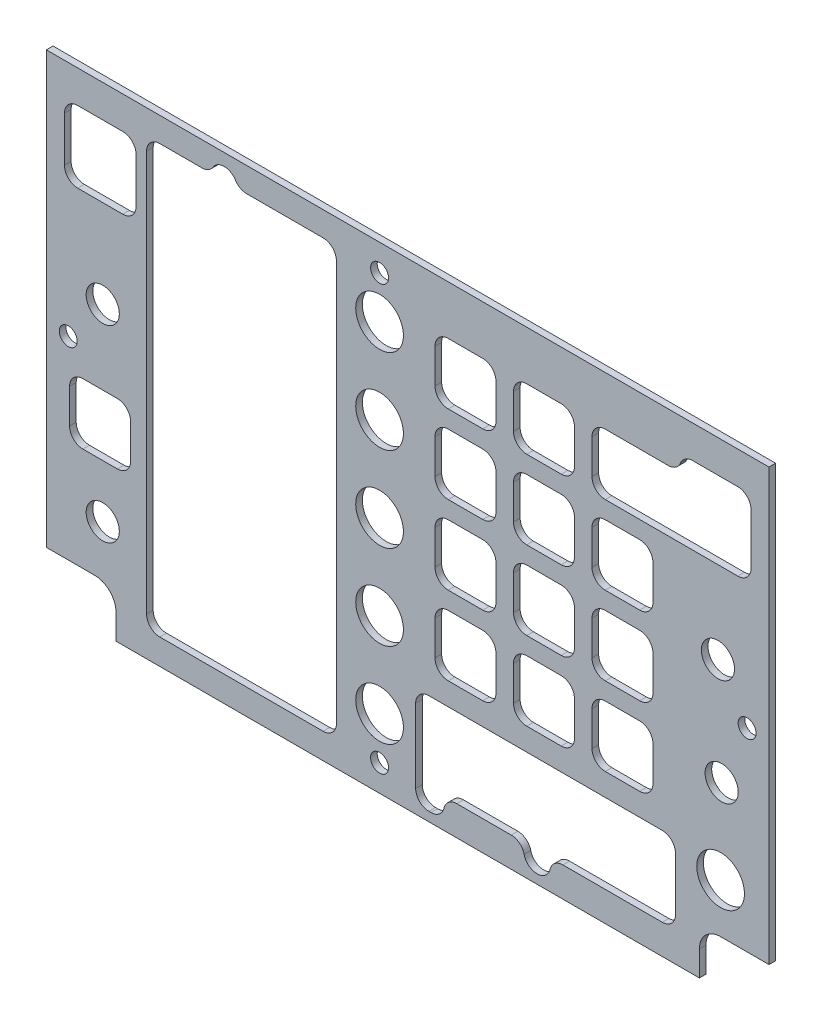
SolidWorks part; units mm, degrees
material "ABS PC"
ref_plane "Front Plane" through (0, 0, 0) normal (0, 0, 1) x (1, 0, 0)
ref_plane "Top Plane" through (0, 0, 0) normal (0, 1, 0) x (1, 0, 0)
ref_plane "Right Plane" through (0, 0, 0) normal (1, 0, 0) x (0, 0, -1)
sketch "Sketch1" plane through (0, 0, 0) normal (0, 0, 1) x (1, 0, 0)
  line L8 (74.93, -171.1167) -> (86.5187, -171.1167)
  line L9 (86.5187, -171.1167) -> (86.5187, -67.9292)
  line L10 (86.5187, -67.9292) -> (-86.5187, -67.9292)
  line L11 (-86.5187, -67.9292) -> (-86.5187, -171.1167)
  line L12 (-86.5187, -171.1167) -> (-74.93, -171.1167)
  line L13 (-69.85, -176.1967) -> (-69.85, -182.2292)
  line L14 (-69.85, -182.2292) -> (69.85, -182.2292)
  line L15 (69.85, -182.2292) -> (69.85, -176.1967)
  line L16 (74.93, -171.1167) -> (86.5187, -171.1167)
  line L17 (86.5187, -171.1167) -> (86.5187, -67.9292)
  line L18 (86.5187, -67.9292) -> (-86.5187, -67.9292)
  line L19 (-86.5187, -67.9292) -> (-86.5187, -171.1167)
  line L20 (-86.5187, -171.1167) -> (-74.93, -171.1167)
  line L21 (-69.85, -176.1967) -> (-69.85, -182.2292)
  line L22 (-69.85, -182.2292) -> (69.85, -182.2292)
  line L23 (69.85, -182.2292) -> (69.85, -176.1967)
  arc A2 (-69.85, -176.1967) -> (-74.93, -171.1167) centre (-74.93, -176.1967) ccw
  arc A3 (74.93, -171.1167) -> (69.85, -176.1967) centre (74.93, -176.1967) ccw
  arc A4 (-69.85, -176.1967) -> (-74.93, -171.1167) centre (-74.93, -176.1967) ccw
  arc A5 (74.93, -171.1167) -> (69.85, -176.1967) centre (74.93, -176.1967) ccw
  dimension "D1" = 0
extrude "Boss-Extrude1" add sketch "Sketch1" against normal blind 1.5875
sketch "Sketch3" plane through (0, 0, 0) normal (0, 0, 1) x (1, 0, 0)
  line L0 (-67.6275, -133.0167) -> (-79.6925, -133.0167) construction
  line L1 (-79.6925, -133.0167) -> (-79.6925, -145.0817) construction
  line L2 (-79.6925, -145.0817) -> (-67.6275, -145.0817) construction
  line L3 (-67.6275, -145.0817) -> (-67.6275, -133.0167) construction
  line L4 (19.8755, -149.3997) -> (19.8755, -137.3347) construction
  line L5 (19.8755, -137.3347) -> (7.8105, -137.3347) construction
  line L6 (7.8105, -137.3347) -> (7.8105, -149.3997) construction
  line L7 (7.8105, -149.3997) -> (19.8755, -149.3997) construction
  line L8 (38.6715, -149.3997) -> (38.6715, -137.3347) construction
  line L9 (38.6715, -137.3347) -> (26.6065, -137.3347) construction
  line L10 (26.6065, -137.3347) -> (26.6065, -149.3997) construction
  line L11 (26.6065, -149.3997) -> (38.6715, -149.3997) construction
  line L12 (45.4025, -149.3997) -> (57.4675, -149.3997) construction
  line L13 (57.4675, -149.3997) -> (57.4675, -137.3347) construction
  line L14 (57.4675, -137.3347) -> (45.4025, -137.3347) construction
  line L15 (45.4025, -137.3347) -> (45.4025, -149.3997) construction
  line L16 (57.4675, -130.6037) -> (57.4675, -118.5387) construction
  line L17 (57.4675, -118.5387) -> (45.4025, -118.5387) construction
  line L18 (45.4025, -118.5387) -> (45.4025, -130.6037) construction
  line L19 (45.4025, -130.6037) -> (57.4675, -130.6037) construction
  line L20 (38.6715, -130.6037) -> (38.6715, -118.5387) construction
  line L21 (38.6715, -118.5387) -> (26.6065, -118.5387) construction
  line L22 (26.6065, -118.5387) -> (26.6065, -130.6037) construction
  line L23 (26.6065, -130.6037) -> (38.6715, -130.6037) construction
  line L24 (19.8755, -130.6037) -> (19.8755, -118.5387) construction
  line L25 (19.8755, -118.5387) -> (7.8105, -118.5387) construction
  line L26 (7.8105, -118.5387) -> (7.8105, -130.6037) construction
  line L27 (7.8105, -130.6037) -> (19.8755, -130.6037) construction
  line L28 (19.8755, -111.8077) -> (19.8755, -99.7427) construction
  line L29 (19.8755, -99.7427) -> (7.8105, -99.7427) construction
  line L30 (7.8105, -99.7427) -> (7.8105, -111.8077) construction
  line L31 (7.8105, -111.8077) -> (19.8755, -111.8077) construction
  line L32 (19.8755, -93.0117) -> (19.8755, -80.9467) construction
  line L33 (19.8755, -80.9467) -> (7.8105, -80.9467) construction
  line L34 (7.8105, -80.9467) -> (7.8105, -93.0117) construction
  line L35 (7.8105, -93.0117) -> (19.8755, -93.0117) construction
  line L36 (38.6715, -93.0117) -> (38.6715, -80.9467) construction
  line L37 (38.6715, -80.9467) -> (26.6065, -80.9467) construction
  line L38 (26.6065, -80.9467) -> (26.6065, -93.0117) construction
  line L39 (26.6065, -93.0117) -> (38.6715, -93.0117) construction
  line L40 (38.6715, -111.8077) -> (38.6715, -99.7427) construction
  line L41 (38.6715, -99.7427) -> (26.6065, -99.7427) construction
  line L42 (26.6065, -99.7427) -> (26.6065, -111.8077) construction
  line L43 (26.6065, -111.8077) -> (38.6715, -111.8077) construction
  line L44 (57.4675, -111.8077) -> (57.4675, -99.7427) construction
  line L45 (57.4675, -99.7427) -> (45.4025, -99.7427) construction
  line L46 (45.4025, -99.7427) -> (45.4025, -111.8077) construction
  line L47 (45.4025, -111.8077) -> (57.4675, -111.8077) construction
  line L48 (57.4675, -93.0117) -> (57.4675, -80.9467) construction
  line L49 (57.4675, -80.9467) -> (45.4025, -80.9467) construction
  line L50 (45.4025, -80.9467) -> (45.4025, -93.0117) construction
  line L51 (45.4025, -93.0117) -> (57.4675, -93.0117) construction
  line L52 (-67.6275, -133.0167) -> (-79.6925, -133.0167)
  line L53 (-79.6925, -133.0167) -> (-79.6925, -145.0817)
  line L54 (-79.6925, -145.0817) -> (-67.6275, -145.0817)
  line L55 (-67.6275, -145.0817) -> (-67.6275, -133.0167)
  line L56 (19.8755, -149.3997) -> (19.8755, -137.3347)
  line L57 (19.8755, -137.3347) -> (7.8105, -137.3347)
  line L58 (7.8105, -137.3347) -> (7.8105, -149.3997)
  line L59 (7.8105, -149.3997) -> (19.8755, -149.3997)
  line L60 (38.6715, -149.3997) -> (38.6715, -137.3347)
  line L61 (38.6715, -137.3347) -> (26.6065, -137.3347)
  line L62 (26.6065, -137.3347) -> (26.6065, -149.3997)
  line L63 (26.6065, -149.3997) -> (38.6715, -149.3997)
  line L64 (45.4025, -149.3997) -> (57.4675, -149.3997)
  line L65 (57.4675, -149.3997) -> (57.4675, -137.3347)
  line L66 (57.4675, -137.3347) -> (45.4025, -137.3347)
  line L67 (45.4025, -137.3347) -> (45.4025, -149.3997)
  line L68 (57.4675, -130.6037) -> (57.4675, -118.5387)
  line L69 (57.4675, -118.5387) -> (45.4025, -118.5387)
  line L70 (45.4025, -118.5387) -> (45.4025, -130.6037)
  line L71 (45.4025, -130.6037) -> (57.4675, -130.6037)
  line L72 (38.6715, -130.6037) -> (38.6715, -118.5387)
  line L73 (38.6715, -118.5387) -> (26.6065, -118.5387)
  line L74 (26.6065, -118.5387) -> (26.6065, -130.6037)
  line L75 (26.6065, -130.6037) -> (38.6715, -130.6037)
  line L76 (19.8755, -130.6037) -> (19.8755, -118.5387)
  line L77 (19.8755, -118.5387) -> (7.8105, -118.5387)
  line L78 (7.8105, -118.5387) -> (7.8105, -130.6037)
  line L79 (7.8105, -130.6037) -> (19.8755, -130.6037)
  line L80 (19.8755, -111.8077) -> (19.8755, -99.7427)
  line L81 (19.8755, -99.7427) -> (7.8105, -99.7427)
  line L82 (7.8105, -99.7427) -> (7.8105, -111.8077)
  line L83 (7.8105, -111.8077) -> (19.8755, -111.8077)
  line L84 (19.8755, -93.0117) -> (19.8755, -80.9467)
  line L85 (19.8755, -80.9467) -> (7.8105, -80.9467)
  line L86 (7.8105, -80.9467) -> (7.8105, -93.0117)
  line L87 (7.8105, -93.0117) -> (19.8755, -93.0117)
  line L88 (38.6715, -93.0117) -> (38.6715, -80.9467)
  line L89 (38.6715, -80.9467) -> (26.6065, -80.9467)
  line L90 (26.6065, -80.9467) -> (26.6065, -93.0117)
  line L91 (26.6065, -93.0117) -> (38.6715, -93.0117)
  line L92 (38.6715, -111.8077) -> (38.6715, -99.7427)
  line L93 (38.6715, -99.7427) -> (26.6065, -99.7427)
  line L94 (26.6065, -99.7427) -> (26.6065, -111.8077)
  line L95 (26.6065, -111.8077) -> (38.6715, -111.8077)
  line L96 (57.4675, -111.8077) -> (57.4675, -99.7427)
  line L97 (57.4675, -99.7427) -> (45.4025, -99.7427)
  line L98 (45.4025, -99.7427) -> (45.4025, -111.8077)
  line L99 (45.4025, -111.8077) -> (57.4675, -111.8077)
  line L100 (57.4675, -93.0117) -> (57.4675, -80.9467)
  line L101 (57.4675, -80.9467) -> (45.4025, -80.9467)
  line L102 (45.4025, -80.9467) -> (45.4025, -93.0117)
  line L103 (45.4025, -93.0117) -> (57.4675, -93.0117)
  circle A0 centre (74.93, -159.3692) radius 4.445 construction
  circle A1 centre (-6.731, -165.7192) radius 4.445 construction
  circle A2 centre (-6.731, -145.3992) radius 4.445 construction
  circle A3 centre (-6.731, -125.0792) radius 4.445 construction
  circle A4 centre (-6.731, -104.7592) radius 4.445 construction
  circle A5 centre (-6.731, -84.4392) radius 4.445 construction
  circle A6 centre (74.93, -159.3692) radius 4.445
  circle A7 centre (-6.731, -165.7192) radius 4.445
  circle A8 centre (-6.731, -145.3992) radius 4.445
  circle A9 centre (-6.731, -125.0792) radius 4.445
  circle A10 centre (-6.731, -104.7592) radius 4.445
  circle A11 centre (-6.731, -84.4392) radius 4.445
extrude "Cut-Extrude1" [suppressed] cut sketch "Sketch3" against normal through all
sketch "Sketch4" plane through (0, 0, 0) normal (0, 0, 1) x (1, 0, 0)
  circle A0 centre (-73.025, -113.9667) radius 3.9688
  circle A1 centre (-73.025, -159.0517) radius 3.9688
  circle A2 centre (74.295, -113.9667) radius 3.9688
  circle A3 centre (75.184, -139.0492) radius 3.9687
  dimension "D1" = 7.9375
extrude "Cut-Extrude2" cut sketch "Sketch4" against normal through all
sketch "Sketch5" plane through (0, 0, 0) normal (0, 0, 1) x (1, 0, 0)
  line L0 (-79.63, -73.9922) -> (-79.63, -94.6322)
  line L1 (-79.63, -94.6322) -> (-67.69, -94.6322)
  line L2 (-67.69, -94.6322) -> (-67.69, -73.9922)
  line L3 (-67.69, -73.9922) -> (-79.63, -73.9922)
  line L4 (-78.36, -75.2622) -> (-78.36, -93.3622)
  line L5 (-78.36, -93.3622) -> (-68.96, -93.3622)
  line L6 (-68.96, -93.3622) -> (-68.96, -75.2622)
  line L7 (-68.96, -75.2622) -> (-78.36, -75.2622)
  line L8 (-78.36, -75.2622) -> (-78.36, -93.3622) construction
  line L9 (-78.36, -93.3622) -> (-68.96, -93.3622) construction
  line L10 (-68.96, -93.3622) -> (-68.96, -75.2622) construction
  line L11 (-68.96, -75.2622) -> (-78.36, -75.2622) construction
  line L12 (68.96, -75.2622) -> (68.96, -93.3622)
  line L13 (68.96, -93.3622) -> (78.36, -93.3622)
  line L14 (78.36, -93.3622) -> (78.36, -75.2622)
  line L15 (78.36, -75.2622) -> (68.96, -75.2622)
  line L16 (68.96, -75.2622) -> (68.96, -93.3622) construction
  line L17 (68.96, -93.3622) -> (78.36, -93.3622) construction
  line L18 (78.36, -93.3622) -> (78.36, -75.2622) construction
  line L19 (78.36, -75.2622) -> (68.96, -75.2622) construction
  line L20 (67.69, -73.9922) -> (67.69, -94.6322)
  line L21 (67.69, -94.6322) -> (79.63, -94.6322)
  line L22 (79.63, -94.6322) -> (79.63, -73.9922)
  line L23 (79.63, -73.9922) -> (67.69, -73.9922)
  line L24 (-61.06, -75.0622) -> (-51.66, -75.0622) construction
  line L25 (-62.53, -73.7922) -> (-17.068, -73.7922)
  line L26 (-62.53, -73.7922) -> (-62.53, -176.1122)
  line L27 (-62.53, -176.1122) -> (-17.068, -176.1122)
  line L28 (-17.068, -73.7922) -> (-17.068, -176.1122)
  line L29 (-62.53, -73.7922) -> (-17.068, -176.1122) construction
  line L30 (-62.53, -176.1122) -> (-17.068, -73.7922) construction
  line L31 (-61.26, -93.3622) -> (-61.26, -75.2622) construction
  line L32 (-51.66, -174.8422) -> (-61.06, -174.8422) construction
  line L33 (-18.338, -167.7344) -> (-18.338, -169.4031) construction
  line L34 (61.52, -158.4422) -> (61.52, -172.5422) construction
  line L35 (5.02, -157.9422) -> (61.02, -157.9422) construction
  line L36 (61.02, -173.0422) -> (5.02, -173.0422) construction
  line L37 (4.52, -172.5422) -> (4.52, -158.4422) construction
  line L38 (61.52, -157.9422) -> (61.52, -173.0422)
  line L39 (4.52, -157.9422) -> (61.52, -157.9422)
  line L40 (61.52, -173.0422) -> (4.52, -173.0422)
  line L41 (4.52, -173.0422) -> (4.52, -157.9422)
  point P20 (-39.799, -124.9522)
  dimension "D4" = 1.27
  dimension "D5" = 1.27
  dimension "D6" = 1.27
  dimension "D7" = 1.27
  dimension "D1" = 0
  dimension "D2" = 0
  dimension "D3" = 1.27
extrude "Cut-Extrude3" [suppressed] cut sketch "Sketch5" against normal through all
sketch "Sketch6" plane through (0, 0, 0) normal (0, 0, 1) x (1, 0, 0)
  line L4 (-67.6275, -133.0167) -> (-79.6925, -133.0167) construction
  line L5 (57.4675, -137.3347) -> (45.4025, -137.3347) construction
  line L6 (45.4025, -137.3347) -> (45.4025, -149.3997) construction
  line L7 (45.4025, -149.3997) -> (57.4675, -149.3997) construction
  line L8 (57.4675, -149.3997) -> (57.4675, -137.3347) construction
  line L9 (45.4025, -130.6037) -> (57.4675, -130.6037) construction
  line L10 (57.4675, -130.6037) -> (57.4675, -118.5387) construction
  line L11 (57.4675, -118.5387) -> (45.4025, -118.5387) construction
  line L12 (45.4025, -118.5387) -> (45.4025, -130.6037) construction
  line L13 (45.4025, -111.8077) -> (57.4675, -111.8077) construction
  line L14 (57.4675, -111.8077) -> (57.4675, -99.7427) construction
  line L15 (57.4675, -99.7427) -> (45.4025, -99.7427) construction
  line L16 (45.4025, -99.7427) -> (45.4025, -111.8077) construction
  line L17 (45.4025, -93.0117) -> (57.4675, -93.0117) construction
  line L18 (57.4675, -93.0117) -> (57.4675, -80.9467) construction
  line L19 (57.4675, -80.9467) -> (45.4025, -80.9467) construction
  line L20 (45.4025, -80.9467) -> (45.4025, -93.0117) construction
  line L21 (26.6065, -149.3997) -> (38.6715, -149.3997) construction
  line L22 (38.6715, -149.3997) -> (38.6715, -137.3347) construction
  line L23 (38.6715, -137.3347) -> (26.6065, -137.3347) construction
  line L24 (26.6065, -137.3347) -> (26.6065, -149.3997) construction
  line L25 (26.6065, -130.6037) -> (38.6715, -130.6037) construction
  line L26 (38.6715, -130.6037) -> (38.6715, -118.5387) construction
  line L27 (38.6715, -118.5387) -> (26.6065, -118.5387) construction
  line L28 (26.6065, -118.5387) -> (26.6065, -130.6037) construction
  line L29 (26.6065, -111.8077) -> (38.6715, -111.8077) construction
  line L30 (38.6715, -111.8077) -> (38.6715, -99.7427) construction
  line L31 (38.6715, -99.7427) -> (26.6065, -99.7427) construction
  line L32 (26.6065, -99.7427) -> (26.6065, -111.8077) construction
  line L33 (26.6065, -93.0117) -> (38.6715, -93.0117) construction
  line L34 (38.6715, -93.0117) -> (38.6715, -80.9467) construction
  line L35 (38.6715, -80.9467) -> (26.6065, -80.9467) construction
  line L36 (26.6065, -80.9467) -> (26.6065, -93.0117) construction
  line L37 (7.8105, -93.0117) -> (19.8755, -93.0117) construction
  line L38 (19.8755, -93.0117) -> (19.8755, -80.9467) construction
  line L39 (19.8755, -80.9467) -> (7.8105, -80.9467) construction
  line L40 (7.8105, -80.9467) -> (7.8105, -93.0117) construction
  line L41 (7.8105, -111.8077) -> (19.8755, -111.8077) construction
  line L42 (19.8755, -111.8077) -> (19.8755, -99.7427) construction
  line L43 (19.8755, -99.7427) -> (7.8105, -99.7427) construction
  line L44 (7.8105, -99.7427) -> (7.8105, -111.8077) construction
  line L45 (19.8755, -118.5387) -> (7.8105, -118.5387) construction
  line L46 (7.8105, -118.5387) -> (7.8105, -130.6037) construction
  line L47 (7.8105, -130.6037) -> (19.8755, -130.6037) construction
  line L48 (19.8755, -130.6037) -> (19.8755, -118.5387) construction
  line L49 (19.8755, -137.3347) -> (7.8105, -137.3347) construction
  line L50 (7.8105, -137.3347) -> (7.8105, -149.3997) construction
  line L51 (7.8105, -149.3997) -> (19.8755, -149.3997) construction
  line L52 (19.8755, -149.3997) -> (19.8755, -137.3347) construction
  line L53 (-79.6925, -133.0167) -> (-79.6925, -145.0817) construction
  line L54 (-79.6925, -145.0817) -> (-67.6275, -145.0817) construction
  line L55 (-67.6275, -145.0817) -> (-67.6275, -133.0167) construction
  line L56 (57.4675, -137.3347) -> (45.4025, -137.3347) construction
  line L57 (45.4025, -137.3347) -> (45.4025, -149.3997) construction
  line L58 (45.4025, -149.3997) -> (57.4675, -149.3997) construction
  line L59 (57.4675, -149.3997) -> (57.4675, -137.3347) construction
  line L60 (45.4025, -130.6037) -> (57.4675, -130.6037) construction
  line L61 (57.4675, -130.6037) -> (57.4675, -118.5387) construction
  line L62 (57.4675, -118.5387) -> (45.4025, -118.5387) construction
  line L63 (45.4025, -118.5387) -> (45.4025, -130.6037) construction
  line L64 (45.4025, -111.8077) -> (57.4675, -111.8077) construction
  line L65 (57.4675, -111.8077) -> (57.4675, -99.7427) construction
  line L66 (57.4675, -99.7427) -> (45.4025, -99.7427) construction
  line L67 (45.4025, -99.7427) -> (45.4025, -111.8077) construction
  line L68 (45.4025, -93.0117) -> (57.4675, -93.0117) construction
  line L69 (57.4675, -93.0117) -> (57.4675, -80.9467) construction
  line L70 (57.4675, -80.9467) -> (45.4025, -80.9467) construction
  line L71 (45.4025, -80.9467) -> (45.4025, -93.0117) construction
  line L72 (26.6065, -149.3997) -> (38.6715, -149.3997) construction
  line L73 (38.6715, -149.3997) -> (38.6715, -137.3347) construction
  line L74 (38.6715, -137.3347) -> (26.6065, -137.3347) construction
  line L75 (26.6065, -137.3347) -> (26.6065, -149.3997) construction
  line L76 (26.6065, -130.6037) -> (38.6715, -130.6037) construction
  line L77 (38.6715, -130.6037) -> (38.6715, -118.5387) construction
  line L78 (38.6715, -118.5387) -> (26.6065, -118.5387) construction
  line L79 (26.6065, -118.5387) -> (26.6065, -130.6037) construction
  line L80 (26.6065, -111.8077) -> (38.6715, -111.8077) construction
  line L81 (38.6715, -111.8077) -> (38.6715, -99.7427) construction
  line L82 (38.6715, -99.7427) -> (26.6065, -99.7427) construction
  line L83 (26.6065, -99.7427) -> (26.6065, -111.8077) construction
  line L84 (26.6065, -93.0117) -> (38.6715, -93.0117) construction
  line L85 (38.6715, -93.0117) -> (38.6715, -80.9467) construction
  line L86 (38.6715, -80.9467) -> (26.6065, -80.9467) construction
  line L87 (26.6065, -80.9467) -> (26.6065, -93.0117) construction
  line L88 (7.8105, -93.0117) -> (19.8755, -93.0117) construction
  line L89 (19.8755, -93.0117) -> (19.8755, -80.9467) construction
  line L90 (19.8755, -80.9467) -> (7.8105, -80.9467) construction
  line L91 (7.8105, -80.9467) -> (7.8105, -93.0117) construction
  line L92 (7.8105, -111.8077) -> (19.8755, -111.8077) construction
  line L93 (19.8755, -111.8077) -> (19.8755, -99.7427) construction
  line L94 (19.8755, -99.7427) -> (7.8105, -99.7427) construction
  line L95 (7.8105, -99.7427) -> (7.8105, -111.8077) construction
  line L96 (19.8755, -118.5387) -> (7.8105, -118.5387) construction
  line L97 (7.8105, -118.5387) -> (7.8105, -130.6037) construction
  line L98 (7.8105, -130.6037) -> (19.8755, -130.6037) construction
  line L99 (19.8755, -130.6037) -> (19.8755, -118.5387) construction
  line L100 (19.8755, -137.3347) -> (7.8105, -137.3347) construction
  line L101 (7.8105, -137.3347) -> (7.8105, -149.3997) construction
  line L102 (7.8105, -149.3997) -> (19.8755, -149.3997) construction
  line L103 (19.8755, -149.3997) -> (19.8755, -137.3347) construction
  line L104 (-67.6275, -133.0167) -> (-79.6925, -133.0167) construction
  line L105 (-79.6925, -133.0167) -> (-79.6925, -145.0817) construction
  line L106 (-79.6925, -145.0817) -> (-67.6275, -145.0817) construction
  line L107 (-67.6275, -145.0817) -> (-67.6275, -133.0167) construction
  line L108 (58.7375, -136.0647) -> (44.1325, -136.0647)
  line L109 (44.1325, -136.0647) -> (44.1325, -150.6697)
  line L110 (44.1325, -150.6697) -> (58.7375, -150.6697)
  line L111 (58.7375, -150.6697) -> (58.7375, -136.0647)
  line L112 (44.1325, -131.8737) -> (58.7375, -131.8737)
  line L113 (58.7375, -131.8737) -> (58.7375, -117.2687)
  line L114 (58.7375, -117.2687) -> (44.1325, -117.2687)
  line L115 (44.1325, -117.2687) -> (44.1325, -131.8737)
  line L116 (44.1325, -113.0777) -> (58.7375, -113.0777)
  line L117 (58.7375, -113.0777) -> (58.7375, -98.4727)
  line L118 (58.7375, -98.4727) -> (44.1325, -98.4727)
  line L119 (44.1325, -98.4727) -> (44.1325, -113.0777)
  line L120 (44.1325, -94.2817) -> (58.7375, -94.2817)
  line L121 (58.7375, -94.2817) -> (58.7375, -79.6767)
  line L122 (58.7375, -79.6767) -> (44.1325, -79.6767)
  line L123 (44.1325, -79.6767) -> (44.1325, -94.2817)
  line L124 (25.3365, -150.6697) -> (39.9415, -150.6697)
  line L125 (39.9415, -150.6697) -> (39.9415, -136.0647)
  line L126 (39.9415, -136.0647) -> (25.3365, -136.0647)
  line L127 (25.3365, -136.0647) -> (25.3365, -150.6697)
  line L128 (25.3365, -131.8737) -> (39.9415, -131.8737)
  line L129 (39.9415, -131.8737) -> (39.9415, -117.2687)
  line L130 (39.9415, -117.2687) -> (25.3365, -117.2687)
  line L131 (25.3365, -117.2687) -> (25.3365, -131.8737)
  line L132 (25.3365, -113.0777) -> (39.9415, -113.0777)
  line L133 (39.9415, -113.0777) -> (39.9415, -98.4727)
  line L134 (39.9415, -98.4727) -> (25.3365, -98.4727)
  line L135 (25.3365, -98.4727) -> (25.3365, -113.0777)
  line L136 (25.3365, -94.2817) -> (39.9415, -94.2817)
  line L137 (39.9415, -94.2817) -> (39.9415, -79.6767)
  line L138 (39.9415, -79.6767) -> (25.3365, -79.6767)
  line L139 (25.3365, -79.6767) -> (25.3365, -94.2817)
  line L140 (6.5405, -94.2817) -> (21.1455, -94.2817)
  line L141 (21.1455, -94.2817) -> (21.1455, -79.6767)
  line L142 (21.1455, -79.6767) -> (6.5405, -79.6767)
  line L143 (6.5405, -79.6767) -> (6.5405, -94.2817)
  line L144 (6.5405, -113.0777) -> (21.1455, -113.0777)
  line L145 (21.1455, -113.0777) -> (21.1455, -98.4727)
  line L146 (21.1455, -98.4727) -> (6.5405, -98.4727)
  line L147 (6.5405, -98.4727) -> (6.5405, -113.0777)
  line L148 (21.1455, -117.2687) -> (6.5405, -117.2687)
  line L149 (6.5405, -117.2687) -> (6.5405, -131.8737)
  line L150 (6.5405, -131.8737) -> (21.1455, -131.8737)
  line L151 (21.1455, -131.8737) -> (21.1455, -117.2687)
  line L152 (21.1455, -136.0647) -> (6.5405, -136.0647)
  line L153 (6.5405, -136.0647) -> (6.5405, -150.6697)
  line L154 (6.5405, -150.6697) -> (21.1455, -150.6697)
  line L155 (21.1455, -150.6697) -> (21.1455, -136.0647)
  line L156 (-66.3575, -131.7467) -> (-80.9625, -131.7467)
  line L157 (-80.9625, -131.7467) -> (-80.9625, -146.3517)
  line L158 (-80.9625, -146.3517) -> (-66.3575, -146.3517)
  line L159 (-66.3575, -146.3517) -> (-66.3575, -131.7467)
  circle A6 centre (74.93, -159.3692) radius 4.445 construction
  circle A7 centre (-6.731, -165.7192) radius 4.445 construction
  circle A9 centre (-6.731, -145.3992) radius 4.445 construction
  circle A12 centre (-6.731, -125.0792) radius 4.445 construction
  circle A16 centre (-6.731, -104.7592) radius 4.445 construction
  circle A21 centre (-6.731, -84.4392) radius 4.445 construction
  circle A33 centre (74.93, -159.3692) radius 4.445 construction
  circle A34 centre (-6.731, -165.7192) radius 4.445 construction
  circle A35 centre (-6.731, -145.3992) radius 4.445 construction
  circle A36 centre (-6.731, -125.0792) radius 4.445 construction
  circle A37 centre (-6.731, -104.7592) radius 4.445 construction
  circle A38 centre (-6.731, -84.4392) radius 4.445 construction
  circle A39 centre (74.93, -159.3692) radius 5.715
  circle A40 centre (-6.731, -165.7192) radius 5.715
  circle A41 centre (-6.731, -145.3992) radius 5.715
  circle A42 centre (-6.731, -125.0792) radius 5.715
  circle A43 centre (-6.731, -104.7592) radius 5.715
  circle A44 centre (-6.731, -84.4392) radius 5.715
  dimension "D1" = 1.27
extrude "Cut-Extrude4" [suppressed] cut sketch "Sketch6" against normal through all
sketch "Sketch7" plane through (0, 0, 0) normal (0, 0, 1) x (1, 0, 0)
  line L0 (66.04, -176.9122) -> (66.04, -148.2722)
  line L1 (66.04, -148.2722) -> (0, -148.2722)
  line L2 (0, -148.2722) -> (0, -176.9122)
  line L3 (0, -176.9122) -> (66.04, -176.9122)
  line L4 (64.77, -175.6422) -> (64.77, -149.5422)
  line L5 (64.77, -149.5422) -> (1.27, -149.5422)
  line L6 (1.27, -149.5422) -> (1.27, -175.6422)
  line L7 (1.27, -175.6422) -> (64.77, -175.6422)
  line L8 (64.77, -175.6422) -> (64.77, -149.5422) construction
  line L9 (64.77, -149.5422) -> (1.27, -149.5422) construction
  line L10 (1.27, -149.5422) -> (1.27, -175.6422) construction
  line L11 (1.27, -175.6422) -> (64.77, -175.6422) construction
  dimension "D1" = 0
  dimension "D2" = 1.27
extrude "Cut-Extrude5" [suppressed] cut sketch "Sketch7" against normal through all
hole_wizard "#6 Clearance Hole2" positions "Sketch10" profile "Sketch11" hole size "#6" standard "ANSI Inch" end condition through all
sketch "Sketch10" plane through (0, 0, 1.5875) normal (0, 0, 1) x (-1, 0, 0)
  point P0 (-81.28, 124.6982)
  point P3 (6.731, 175.8792)
  point P6 (81.28, 124.6982)
  point P9 (6.731, 74.2792)
sketch "Sketch11" plane through (81.28, -124.6982, 1.5875) normal (1, 0, 0) x (0, -1, 0)
  line L0 (0, 0) -> (0, 3.175)
  line L1 (0, 3.175) -> (2.1526, 3.175)
  line L2 (2.1526, 3.175) -> (2.1526, 0)
  line L3 (2.1526, 0) -> (0, 0)
  line L4 (0, -6.35) -> (0, 107.95) construction
  dimension "Thru Hole Dia." = 4.3053
  dimension "Thru Hole Depth" = 3.175
sketch "Sketch12" plane through (0, 0, -1.5875) normal (0, 0, -1) x (-1, 0, 0)
  line L0 (73.6125, -76.7792) -> (73.6125, -91.7792) construction
  line L1 (-73.6482, -76.8365) -> (-73.6482, -91.8365) construction
  line L4 (66.1125, -76.7792) -> (66.1125, -91.7792)
  line L5 (81.1125, -76.7792) -> (66.1125, -76.7792)
  line L6 (66.1125, -91.7792) -> (81.1125, -91.7792)
  line L7 (81.1125, -91.7792) -> (81.1125, -76.7792)
  line L10 (-81.1482, -76.8365) -> (-81.1482, -91.8365)
  line L11 (-66.1482, -91.8365) -> (-66.1482, -76.8365)
  line L12 (-66.1482, -91.8365) -> (-81.1482, -91.8365)
  line L13 (-81.1482, -76.8365) -> (-66.1482, -76.8365)
  point P12 (-73.6482, -84.3365)
  point P13 (73.6125, -84.2792)
  dimension "D1" = 15
extrude "Cut-Extrude6" [suppressed] cut sketch "Sketch12" against normal up to next
sketch "Sketch15" plane through (0, 0, -1.5875) normal (0, 0, -1) x (-1, 0, 0)
  line L4 (-58.7375, -139.2397) -> (-58.7375, -147.4947)
  line L5 (-47.3075, -136.0647) -> (-55.5625, -136.0647)
  line L6 (-44.1325, -147.4947) -> (-44.1325, -139.2397)
  line L7 (-55.5625, -150.6697) -> (-47.3075, -150.6697)
  line L8 (-58.7375, -139.2397) -> (-58.7375, -147.4947)
  line L9 (-47.3075, -136.0647) -> (-55.5625, -136.0647)
  line L10 (-44.1325, -147.4947) -> (-44.1325, -139.2397)
  line L11 (-55.5625, -150.6697) -> (-47.3075, -150.6697)
  line L12 (-58.7375, -120.4437) -> (-58.7375, -128.6987)
  line L13 (-47.3075, -117.2687) -> (-55.5625, -117.2687)
  line L14 (-44.1325, -128.6987) -> (-44.1325, -120.4437)
  line L15 (-55.5625, -131.8737) -> (-47.3075, -131.8737)
  line L16 (-58.7375, -120.4437) -> (-58.7375, -128.6987)
  line L17 (-47.3075, -117.2687) -> (-55.5625, -117.2687)
  line L18 (-44.1325, -128.6987) -> (-44.1325, -120.4437)
  line L19 (-55.5625, -131.8737) -> (-47.3075, -131.8737)
  line L20 (-58.7375, -101.6477) -> (-58.7375, -109.9027)
  line L21 (-47.3075, -98.4727) -> (-55.5625, -98.4727)
  line L22 (-44.1325, -109.9027) -> (-44.1325, -101.6477)
  line L23 (-55.5625, -113.0777) -> (-47.3075, -113.0777)
  line L24 (-58.7375, -101.6477) -> (-58.7375, -109.9027)
  line L25 (-47.3075, -98.4727) -> (-55.5625, -98.4727)
  line L26 (-44.1325, -109.9027) -> (-44.1325, -101.6477)
  line L27 (-55.5625, -113.0777) -> (-47.3075, -113.0777)
  line L28 (-39.9415, -82.8517) -> (-39.9415, -91.1067)
  line L29 (-47.3075, -79.6767) -> (-62.3771, -79.6767)
  line L30 (-44.1325, -91.1067) -> (-44.1325, -82.8517)
  line L31 (-79.0457, -94.2817) -> (-47.3075, -94.2817)
  line L32 (-82.2207, -78.9147) -> (-82.2207, -91.1067)
  line L33 (-68.2507, -75.7397) -> (-79.0457, -75.7397)
  line L34 (-47.3075, -79.6767) -> (-62.3771, -79.6767)
  line L35 (-44.1325, -91.1067) -> (-44.1325, -82.8517)
  line L36 (-79.0457, -94.2817) -> (-47.3075, -94.2817)
  line L37 (-82.2207, -78.9147) -> (-82.2207, -91.1067)
  line L38 (-68.2507, -75.7397) -> (-79.0457, -75.7397)
  line L39 (-28.5115, -79.6767) -> (-36.7665, -79.6767)
  line L40 (-25.3365, -91.1067) -> (-25.3365, -82.8517)
  line L41 (-36.7665, -94.2817) -> (-28.5115, -94.2817)
  line L42 (-39.9415, -82.8517) -> (-39.9415, -91.1067)
  line L43 (-28.5115, -79.6767) -> (-36.7665, -79.6767)
  line L44 (-25.3365, -91.1067) -> (-25.3365, -82.8517)
  line L45 (-36.7665, -94.2817) -> (-28.5115, -94.2817)
  line L46 (-39.9415, -101.6477) -> (-39.9415, -109.9027)
  line L47 (-28.5115, -98.4727) -> (-36.7665, -98.4727)
  line L48 (-25.3365, -109.9027) -> (-25.3365, -101.6477)
  line L49 (-36.7665, -113.0777) -> (-28.5115, -113.0777)
  line L50 (-39.9415, -101.6477) -> (-39.9415, -109.9027)
  line L51 (-28.5115, -98.4727) -> (-36.7665, -98.4727)
  line L52 (-25.3365, -109.9027) -> (-25.3365, -101.6477)
  line L53 (-36.7665, -113.0777) -> (-28.5115, -113.0777)
  line L54 (-39.9415, -120.4437) -> (-39.9415, -128.6987)
  line L55 (-28.5115, -117.2687) -> (-36.7665, -117.2687)
  line L56 (-25.3365, -128.6987) -> (-25.3365, -120.4437)
  line L57 (-36.7665, -131.8737) -> (-28.5115, -131.8737)
  line L58 (-39.9415, -120.4437) -> (-39.9415, -128.6987)
  line L59 (-28.5115, -117.2687) -> (-36.7665, -117.2687)
  line L60 (-25.3365, -128.6987) -> (-25.3365, -120.4437)
  line L61 (-36.7665, -131.8737) -> (-28.5115, -131.8737)
  line L62 (-39.9415, -139.2397) -> (-39.9415, -147.4947)
  line L63 (-28.5115, -136.0647) -> (-36.7665, -136.0647)
  line L64 (-25.3365, -147.4947) -> (-25.3365, -139.2397)
  line L65 (-36.7665, -150.6697) -> (-28.5115, -150.6697)
  line L66 (-39.9415, -139.2397) -> (-39.9415, -147.4947)
  line L67 (-28.5115, -136.0647) -> (-36.7665, -136.0647)
  line L68 (-25.3365, -147.4947) -> (-25.3365, -139.2397)
  line L69 (-36.7665, -150.6697) -> (-28.5115, -150.6697)
  line L70 (-6.5405, -147.4947) -> (-6.5405, -139.2397)
  line L71 (-17.9705, -150.6697) -> (-9.7155, -150.6697)
  line L72 (-24.8003, -175.1172) -> (-11.7797, -175.1172)
  line L73 (-60.96, -175.1172) -> (-37.1797, -175.1172)
  line L74 (-64.135, -159.2422) -> (-64.135, -171.9422)
  line L75 (-5.08, -156.0672) -> (-60.96, -156.0672)
  line L76 (-1.905, -176.8742) -> (-1.905, -159.2422)
  line L77 (-5.59, -180.0492) -> (-5.08, -180.0492)
  line L78 (-24.8003, -175.1172) -> (-11.7797, -175.1172)
  line L79 (-60.96, -175.1172) -> (-37.1797, -175.1172)
  line L80 (-64.135, -159.2422) -> (-64.135, -171.9422)
  line L81 (-5.08, -156.0672) -> (-60.96, -156.0672)
  line L82 (-1.905, -176.8742) -> (-1.905, -159.2422)
  line L83 (-5.59, -180.0492) -> (-5.08, -180.0492)
  line L84 (-21.1455, -139.2397) -> (-21.1455, -147.4947)
  line L85 (-9.7155, -136.0647) -> (-17.9705, -136.0647)
  line L86 (-6.5405, -147.4947) -> (-6.5405, -139.2397)
  line L87 (-17.9705, -150.6697) -> (-9.7155, -150.6697)
  line L88 (-21.1455, -139.2397) -> (-21.1455, -147.4947)
  line L89 (-9.7155, -136.0647) -> (-17.9705, -136.0647)
  line L90 (-6.5405, -128.6987) -> (-6.5405, -120.4437)
  line L91 (-17.9705, -131.8737) -> (-9.7155, -131.8737)
  line L92 (-21.1455, -120.4437) -> (-21.1455, -128.6987)
  line L93 (-9.7155, -117.2687) -> (-17.9705, -117.2687)
  line L94 (-6.5405, -128.6987) -> (-6.5405, -120.4437)
  line L95 (-17.9705, -131.8737) -> (-9.7155, -131.8737)
  line L96 (-21.1455, -120.4437) -> (-21.1455, -128.6987)
  line L97 (-9.7155, -117.2687) -> (-17.9705, -117.2687)
  line L98 (-21.1455, -101.6477) -> (-21.1455, -109.9027)
  line L99 (-9.7155, -98.4727) -> (-17.9705, -98.4727)
  line L100 (-6.5405, -109.9027) -> (-6.5405, -101.6477)
  line L101 (-17.9705, -113.0777) -> (-9.7155, -113.0777)
  line L102 (-21.1455, -101.6477) -> (-21.1455, -109.9027)
  line L103 (-9.7155, -98.4727) -> (-17.9705, -98.4727)
  line L104 (-6.5405, -109.9027) -> (-6.5405, -101.6477)
  line L105 (-17.9705, -113.0777) -> (-9.7155, -113.0777)
  line L106 (-21.1455, -82.8517) -> (-21.1455, -91.1067)
  line L107 (-9.7155, -79.6767) -> (-17.9705, -79.6767)
  line L108 (-6.5405, -91.1067) -> (-6.5405, -82.8517)
  line L109 (-17.9705, -94.2817) -> (-9.7155, -94.2817)
  line L110 (-21.1455, -82.8517) -> (-21.1455, -91.1067)
  line L111 (-9.7155, -79.6767) -> (-17.9705, -79.6767)
  line L112 (-6.5405, -91.1067) -> (-6.5405, -82.8517)
  line L113 (-17.9705, -94.2817) -> (-9.7155, -94.2817)
  line L114 (65.04, -78.8982) -> (65.04, -89.6932)
  line L115 (38.5687, -73.7922) -> (20.243, -73.7922)
  line L116 (59.355, -73.7922) -> (49.3113, -73.7922)
  line L117 (62.53, -172.9372) -> (62.53, -76.9672)
  line L118 (20.243, -176.1122) -> (59.355, -176.1122)
  line L119 (17.068, -76.9672) -> (17.068, -172.9372)
  line L120 (38.5687, -73.7922) -> (20.243, -73.7922)
  line L121 (59.355, -73.7922) -> (49.3113, -73.7922)
  line L122 (62.53, -172.9372) -> (62.53, -76.9672)
  line L123 (20.243, -176.1122) -> (59.355, -176.1122)
  line L124 (17.068, -76.9672) -> (17.068, -172.9372)
  line L125 (79.01, -75.7232) -> (68.215, -75.7232)
  line L126 (82.185, -89.6932) -> (82.185, -78.8982)
  line L127 (68.215, -92.8682) -> (79.01, -92.8682)
  line L128 (65.04, -78.8982) -> (65.04, -89.6932)
  line L129 (79.01, -75.7232) -> (68.215, -75.7232)
  line L130 (82.185, -89.6932) -> (82.185, -78.8982)
  line L131 (68.215, -92.8682) -> (79.01, -92.8682)
  line L132 (80.9625, -143.1767) -> (80.9625, -134.9217)
  line L133 (69.5325, -146.3517) -> (77.7875, -146.3517)
  line L134 (66.3575, -134.9217) -> (66.3575, -143.1767)
  line L135 (77.7875, -131.7467) -> (69.5325, -131.7467)
  line L136 (80.9625, -143.1767) -> (80.9625, -134.9217)
  line L137 (69.5325, -146.3517) -> (77.7875, -146.3517)
  line L138 (66.3575, -134.9217) -> (66.3575, -143.1767)
  line L139 (77.7875, -131.7467) -> (69.5325, -131.7467)
  circle A1 centre (-74.93, -159.3692) radius 5.715
  circle A2 centre (-74.93, -159.3692) radius 5.715
  circle A3 centre (6.731, -84.4392) radius 5.715
  circle A4 centre (6.731, -84.4392) radius 5.715
  circle A5 centre (6.731, -104.7592) radius 5.715
  arc A6 (-55.5625, -136.0647) -> (-58.7375, -139.2397) centre (-55.5625, -139.2397) ccw
  arc A7 (-44.1325, -139.2397) -> (-47.3075, -136.0647) centre (-47.3075, -139.2397) ccw
  arc A8 (-47.3075, -150.6697) -> (-44.1325, -147.4947) centre (-47.3075, -147.4947) ccw
  arc A9 (-58.7375, -147.4947) -> (-55.5625, -150.6697) centre (-55.5625, -147.4947) ccw
  arc A10 (-55.5625, -136.0647) -> (-58.7375, -139.2397) centre (-55.5625, -139.2397) ccw
  arc A11 (-44.1325, -139.2397) -> (-47.3075, -136.0647) centre (-47.3075, -139.2397) ccw
  arc A12 (-47.3075, -150.6697) -> (-44.1325, -147.4947) centre (-47.3075, -147.4947) ccw
  arc A13 (-58.7375, -147.4947) -> (-55.5625, -150.6697) centre (-55.5625, -147.4947) ccw
  arc A14 (-55.5625, -117.2687) -> (-58.7375, -120.4437) centre (-55.5625, -120.4437) ccw
  arc A15 (-44.1325, -120.4437) -> (-47.3075, -117.2687) centre (-47.3075, -120.4437) ccw
  arc A16 (-47.3075, -131.8737) -> (-44.1325, -128.6987) centre (-47.3075, -128.6987) ccw
  arc A17 (-58.7375, -128.6987) -> (-55.5625, -131.8737) centre (-55.5625, -128.6987) ccw
  arc A18 (-55.5625, -117.2687) -> (-58.7375, -120.4437) centre (-55.5625, -120.4437) ccw
  arc A19 (-44.1325, -120.4437) -> (-47.3075, -117.2687) centre (-47.3075, -120.4437) ccw
  arc A20 (-47.3075, -131.8737) -> (-44.1325, -128.6987) centre (-47.3075, -128.6987) ccw
  arc A21 (-58.7375, -128.6987) -> (-55.5625, -131.8737) centre (-55.5625, -128.6987) ccw
  arc A22 (-55.5625, -98.4727) -> (-58.7375, -101.6477) centre (-55.5625, -101.6477) ccw
  arc A23 (-44.1325, -101.6477) -> (-47.3075, -98.4727) centre (-47.3075, -101.6477) ccw
  arc A24 (-47.3075, -113.0777) -> (-44.1325, -109.9027) centre (-47.3075, -109.9027) ccw
  arc A25 (-58.7375, -109.9027) -> (-55.5625, -113.0777) centre (-55.5625, -109.9027) ccw
  arc A26 (-55.5625, -98.4727) -> (-58.7375, -101.6477) centre (-55.5625, -101.6477) ccw
  arc A27 (-44.1325, -101.6477) -> (-47.3075, -98.4727) centre (-47.3075, -101.6477) ccw
  arc A28 (-47.3075, -113.0777) -> (-44.1325, -109.9027) centre (-47.3075, -109.9027) ccw
  arc A29 (-58.7375, -109.9027) -> (-55.5625, -113.0777) centre (-55.5625, -109.9027) ccw
  arc A30 (-36.7665, -79.6767) -> (-39.9415, -82.8517) centre (-36.7665, -82.8517) ccw
  arc A31 (-25.3365, -82.8517) -> (-28.5115, -79.6767) centre (-28.5115, -82.8517) ccw
  arc A32 (-65.3139, -77.7082) -> (-68.2507, -75.7397) centre (-68.2507, -78.9147) ccw
  arc A33 (-65.3139, -77.7082) -> (-62.3771, -79.6767) centre (-62.3771, -76.5017) ccw
  arc A34 (-44.1325, -82.8517) -> (-47.3075, -79.6767) centre (-47.3075, -82.8517) ccw
  arc A35 (-47.3075, -94.2817) -> (-44.1325, -91.1067) centre (-47.3075, -91.1067) ccw
  arc A36 (-82.2207, -91.1067) -> (-79.0457, -94.2817) centre (-79.0457, -91.1067) ccw
  arc A37 (-79.0457, -75.7397) -> (-82.2207, -78.9147) centre (-79.0457, -78.9147) ccw
  arc A38 (-65.3139, -77.7082) -> (-68.2507, -75.7397) centre (-68.2507, -78.9147) ccw
  arc A39 (-65.3139, -77.7082) -> (-62.3771, -79.6767) centre (-62.3771, -76.5017) ccw
  arc A40 (-44.1325, -82.8517) -> (-47.3075, -79.6767) centre (-47.3075, -82.8517) ccw
  arc A41 (-47.3075, -94.2817) -> (-44.1325, -91.1067) centre (-47.3075, -91.1067) ccw
  arc A42 (-82.2207, -91.1067) -> (-79.0457, -94.2817) centre (-79.0457, -91.1067) ccw
  arc A43 (-79.0457, -75.7397) -> (-82.2207, -78.9147) centre (-79.0457, -78.9147) ccw
  arc A44 (-28.5115, -94.2817) -> (-25.3365, -91.1067) centre (-28.5115, -91.1067) ccw
  arc A45 (-39.9415, -91.1067) -> (-36.7665, -94.2817) centre (-36.7665, -91.1067) ccw
  arc A46 (-36.7665, -79.6767) -> (-39.9415, -82.8517) centre (-36.7665, -82.8517) ccw
  arc A47 (-25.3365, -82.8517) -> (-28.5115, -79.6767) centre (-28.5115, -82.8517) ccw
  arc A48 (-28.5115, -94.2817) -> (-25.3365, -91.1067) centre (-28.5115, -91.1067) ccw
  arc A49 (-39.9415, -91.1067) -> (-36.7665, -94.2817) centre (-36.7665, -91.1067) ccw
  arc A50 (-36.7665, -98.4727) -> (-39.9415, -101.6477) centre (-36.7665, -101.6477) ccw
  arc A51 (-25.3365, -101.6477) -> (-28.5115, -98.4727) centre (-28.5115, -101.6477) ccw
  arc A52 (-28.5115, -113.0777) -> (-25.3365, -109.9027) centre (-28.5115, -109.9027) ccw
  arc A53 (-39.9415, -109.9027) -> (-36.7665, -113.0777) centre (-36.7665, -109.9027) ccw
  arc A54 (-36.7665, -98.4727) -> (-39.9415, -101.6477) centre (-36.7665, -101.6477) ccw
  arc A55 (-25.3365, -101.6477) -> (-28.5115, -98.4727) centre (-28.5115, -101.6477) ccw
  arc A56 (-28.5115, -113.0777) -> (-25.3365, -109.9027) centre (-28.5115, -109.9027) ccw
  arc A57 (-39.9415, -109.9027) -> (-36.7665, -113.0777) centre (-36.7665, -109.9027) ccw
  arc A58 (-36.7665, -117.2687) -> (-39.9415, -120.4437) centre (-36.7665, -120.4437) ccw
  arc A59 (-25.3365, -120.4437) -> (-28.5115, -117.2687) centre (-28.5115, -120.4437) ccw
  arc A60 (-28.5115, -131.8737) -> (-25.3365, -128.6987) centre (-28.5115, -128.6987) ccw
  arc A61 (-39.9415, -128.6987) -> (-36.7665, -131.8737) centre (-36.7665, -128.6987) ccw
  arc A62 (-36.7665, -117.2687) -> (-39.9415, -120.4437) centre (-36.7665, -120.4437) ccw
  arc A63 (-25.3365, -120.4437) -> (-28.5115, -117.2687) centre (-28.5115, -120.4437) ccw
  arc A64 (-28.5115, -131.8737) -> (-25.3365, -128.6987) centre (-28.5115, -128.6987) ccw
  arc A65 (-39.9415, -128.6987) -> (-36.7665, -131.8737) centre (-36.7665, -128.6987) ccw
  arc A66 (-36.7665, -136.0647) -> (-39.9415, -139.2397) centre (-36.7665, -139.2397) ccw
  arc A67 (-25.3365, -139.2397) -> (-28.5115, -136.0647) centre (-28.5115, -139.2397) ccw
  arc A68 (-28.5115, -150.6697) -> (-25.3365, -147.4947) centre (-28.5115, -147.4947) ccw
  arc A69 (-39.9415, -147.4947) -> (-36.7665, -150.6697) centre (-36.7665, -147.4947) ccw
  arc A70 (-36.7665, -136.0647) -> (-39.9415, -139.2397) centre (-36.7665, -139.2397) ccw
  arc A71 (-25.3365, -139.2397) -> (-28.5115, -136.0647) centre (-28.5115, -139.2397) ccw
  arc A72 (-28.5115, -150.6697) -> (-25.3365, -147.4947) centre (-28.5115, -147.4947) ccw
  arc A73 (-39.9415, -147.4947) -> (-36.7665, -150.6697) centre (-36.7665, -147.4947) ccw
  arc A74 (-9.7155, -150.6697) -> (-6.5405, -147.4947) centre (-9.7155, -147.4947) ccw
  arc A75 (-21.1455, -147.4947) -> (-17.9705, -150.6697) centre (-17.9705, -147.4947) ccw
  arc A76 (-17.9705, -136.0647) -> (-21.1455, -139.2397) centre (-17.9705, -139.2397) ccw
  arc A77 (-6.5405, -139.2397) -> (-9.7155, -136.0647) centre (-9.7155, -139.2397) ccw
  arc A78 (-9.7155, -150.6697) -> (-6.5405, -147.4947) centre (-9.7155, -147.4947) ccw
  arc A79 (-8.6848, -177.5832) -> (-5.59, -180.0492) centre (-5.59, -176.8742) ccw
  arc A80 (-8.6848, -177.5832) -> (-11.7797, -175.1172) centre (-11.7797, -178.2922) ccw
  arc A81 (-24.8003, -175.1172) -> (-27.8952, -177.5832) centre (-24.8003, -178.2922) ccw
  arc A82 (-34.0848, -177.5832) -> (-27.8952, -177.5832) centre (-30.99, -176.8742) ccw
  arc A83 (-34.0848, -177.5832) -> (-37.1797, -175.1172) centre (-37.1797, -178.2922) ccw
  arc A84 (-64.135, -171.9422) -> (-60.96, -175.1172) centre (-60.96, -171.9422) ccw
  arc A85 (-60.96, -156.0672) -> (-64.135, -159.2422) centre (-60.96, -159.2422) ccw
  arc A86 (-1.905, -159.2422) -> (-5.08, -156.0672) centre (-5.08, -159.2422) ccw
  arc A87 (-5.08, -180.0492) -> (-1.905, -176.8742) centre (-5.08, -176.8742) ccw
  arc A88 (-8.6848, -177.5832) -> (-5.59, -180.0492) centre (-5.59, -176.8742) ccw
  arc A89 (-8.6848, -177.5832) -> (-11.7797, -175.1172) centre (-11.7797, -178.2922) ccw
  arc A90 (-24.8003, -175.1172) -> (-27.8952, -177.5832) centre (-24.8003, -178.2922) ccw
  arc A91 (-34.0848, -177.5832) -> (-27.8952, -177.5832) centre (-30.99, -176.8742) ccw
  arc A92 (-34.0848, -177.5832) -> (-37.1797, -175.1172) centre (-37.1797, -178.2922) ccw
  arc A93 (-64.135, -171.9422) -> (-60.96, -175.1172) centre (-60.96, -171.9422) ccw
  arc A94 (-60.96, -156.0672) -> (-64.135, -159.2422) centre (-60.96, -159.2422) ccw
  arc A95 (-1.905, -159.2422) -> (-5.08, -156.0672) centre (-5.08, -159.2422) ccw
  arc A96 (-5.08, -180.0492) -> (-1.905, -176.8742) centre (-5.08, -176.8742) ccw
  arc A97 (-21.1455, -147.4947) -> (-17.9705, -150.6697) centre (-17.9705, -147.4947) ccw
  arc A98 (-17.9705, -136.0647) -> (-21.1455, -139.2397) centre (-17.9705, -139.2397) ccw
  arc A99 (-6.5405, -139.2397) -> (-9.7155, -136.0647) centre (-9.7155, -139.2397) ccw
  arc A100 (-9.7155, -131.8737) -> (-6.5405, -128.6987) centre (-9.7155, -128.6987) ccw
  arc A101 (-21.1455, -128.6987) -> (-17.9705, -131.8737) centre (-17.9705, -128.6987) ccw
  arc A102 (-17.9705, -117.2687) -> (-21.1455, -120.4437) centre (-17.9705, -120.4437) ccw
  arc A103 (-6.5405, -120.4437) -> (-9.7155, -117.2687) centre (-9.7155, -120.4437) ccw
  arc A104 (-9.7155, -131.8737) -> (-6.5405, -128.6987) centre (-9.7155, -128.6987) ccw
  arc A105 (-21.1455, -128.6987) -> (-17.9705, -131.8737) centre (-17.9705, -128.6987) ccw
  arc A106 (-17.9705, -117.2687) -> (-21.1455, -120.4437) centre (-17.9705, -120.4437) ccw
  arc A107 (-6.5405, -120.4437) -> (-9.7155, -117.2687) centre (-9.7155, -120.4437) ccw
  arc A108 (-17.9705, -98.4727) -> (-21.1455, -101.6477) centre (-17.9705, -101.6477) ccw
  arc A109 (-6.5405, -101.6477) -> (-9.7155, -98.4727) centre (-9.7155, -101.6477) ccw
  arc A110 (-9.7155, -113.0777) -> (-6.5405, -109.9027) centre (-9.7155, -109.9027) ccw
  arc A111 (-21.1455, -109.9027) -> (-17.9705, -113.0777) centre (-17.9705, -109.9027) ccw
  arc A112 (-17.9705, -98.4727) -> (-21.1455, -101.6477) centre (-17.9705, -101.6477) ccw
  arc A113 (-6.5405, -101.6477) -> (-9.7155, -98.4727) centre (-9.7155, -101.6477) ccw
  arc A114 (-9.7155, -113.0777) -> (-6.5405, -109.9027) centre (-9.7155, -109.9027) ccw
  arc A115 (-21.1455, -109.9027) -> (-17.9705, -113.0777) centre (-17.9705, -109.9027) ccw
  arc A116 (-17.9705, -79.6767) -> (-21.1455, -82.8517) centre (-17.9705, -82.8517) ccw
  arc A117 (-6.5405, -82.8517) -> (-9.7155, -79.6767) centre (-9.7155, -82.8517) ccw
  arc A118 (-9.7155, -94.2817) -> (-6.5405, -91.1067) centre (-9.7155, -91.1067) ccw
  arc A119 (-21.1455, -91.1067) -> (-17.9705, -94.2817) centre (-17.9705, -91.1067) ccw
  arc A120 (-17.9705, -79.6767) -> (-21.1455, -82.8517) centre (-17.9705, -82.8517) ccw
  arc A121 (-6.5405, -82.8517) -> (-9.7155, -79.6767) centre (-9.7155, -82.8517) ccw
  arc A122 (-9.7155, -94.2817) -> (-6.5405, -91.1067) centre (-9.7155, -91.1067) ccw
  arc A123 (-21.1455, -91.1067) -> (-17.9705, -94.2817) centre (-17.9705, -91.1067) ccw
  circle A124 centre (6.731, -104.7592) radius 5.715
  circle A125 centre (6.731, -125.0792) radius 5.715
  circle A126 centre (6.731, -125.0792) radius 5.715
  circle A127 centre (6.731, -145.3992) radius 5.715
  circle A128 centre (6.731, -145.3992) radius 5.715
  circle A129 centre (6.731, -165.7192) radius 5.715
  circle A130 centre (6.731, -165.7192) radius 5.715
  arc A134 (68.215, -75.7232) -> (65.04, -78.8982) centre (68.215, -78.8982) ccw
  arc A135 (82.185, -78.8982) -> (79.01, -75.7232) centre (79.01, -78.8982) ccw
  arc A136 (79.01, -92.8682) -> (82.185, -89.6932) centre (79.01, -89.6932) ccw
  arc A137 (38.5687, -73.7922) -> (41.2544, -72.3107) centre (38.5687, -70.6172) ccw
  arc A138 (46.6256, -72.3107) -> (41.2544, -72.3107) centre (43.94, -74.0042) ccw
  arc A139 (46.6256, -72.3107) -> (49.3113, -73.7922) centre (49.3113, -70.6172) ccw
  arc A140 (62.53, -76.9672) -> (59.355, -73.7922) centre (59.355, -76.9672) ccw
  arc A141 (59.355, -176.1122) -> (62.53, -172.9372) centre (59.355, -172.9372) ccw
  arc A142 (17.068, -172.9372) -> (20.243, -176.1122) centre (20.243, -172.9372) ccw
  arc A143 (20.243, -73.7922) -> (17.068, -76.9672) centre (20.243, -76.9672) ccw
  arc A144 (38.5687, -73.7922) -> (41.2544, -72.3107) centre (38.5687, -70.6172) ccw
  arc A145 (46.6256, -72.3107) -> (41.2544, -72.3107) centre (43.94, -74.0042) ccw
  arc A146 (46.6256, -72.3107) -> (49.3113, -73.7922) centre (49.3113, -70.6172) ccw
  arc A147 (62.53, -76.9672) -> (59.355, -73.7922) centre (59.355, -76.9672) ccw
  arc A148 (59.355, -176.1122) -> (62.53, -172.9372) centre (59.355, -172.9372) ccw
  arc A149 (17.068, -172.9372) -> (20.243, -176.1122) centre (20.243, -172.9372) ccw
  arc A150 (20.243, -73.7922) -> (17.068, -76.9672) centre (20.243, -76.9672) ccw
  arc A151 (65.04, -89.6932) -> (68.215, -92.8682) centre (68.215, -89.6932) ccw
  arc A152 (68.215, -75.7232) -> (65.04, -78.8982) centre (68.215, -78.8982) ccw
  arc A153 (82.185, -78.8982) -> (79.01, -75.7232) centre (79.01, -78.8982) ccw
  arc A154 (79.01, -92.8682) -> (82.185, -89.6932) centre (79.01, -89.6932) ccw
  arc A155 (65.04, -89.6932) -> (68.215, -92.8682) centre (68.215, -89.6932) ccw
  arc A156 (77.7875, -146.3517) -> (80.9625, -143.1767) centre (77.7875, -143.1767) ccw
  arc A157 (66.3575, -143.1767) -> (69.5325, -146.3517) centre (69.5325, -143.1767) ccw
  arc A158 (69.5325, -131.7467) -> (66.3575, -134.9217) centre (69.5325, -134.9217) ccw
  arc A159 (80.9625, -134.9217) -> (77.7875, -131.7467) centre (77.7875, -134.9217) ccw
  arc A160 (77.7875, -146.3517) -> (80.9625, -143.1767) centre (77.7875, -143.1767) ccw
  arc A161 (66.3575, -143.1767) -> (69.5325, -146.3517) centre (69.5325, -143.1767) ccw
  arc A162 (69.5325, -131.7467) -> (66.3575, -134.9217) centre (69.5325, -134.9217) ccw
  arc A163 (80.9625, -134.9217) -> (77.7875, -131.7467) centre (77.7875, -134.9217) ccw
  dimension "D1" = 0
  dimension "D2" = 0
  dimension "D3" = 0
  dimension "D4" = 0
  dimension "D5" = 0
  dimension "D6" = 0
  dimension "D7" = 0
  dimension "D8" = 0
  dimension "D9" = 0
  dimension "D10" = 0
  dimension "D11" = 0
  dimension "D12" = 0
  dimension "D13" = 0
  dimension "D14" = 0
  dimension "D15" = 0
  dimension "D16" = 0
  dimension "D17" = 0
  dimension "D18" = 0
  dimension "D19" = 0
  dimension "D20" = 0
  dimension "D21" = 0
  dimension "D22" = 0
extrude "Cut-Extrude8" cut sketch "Sketch15" against normal through all both and the other way through all
